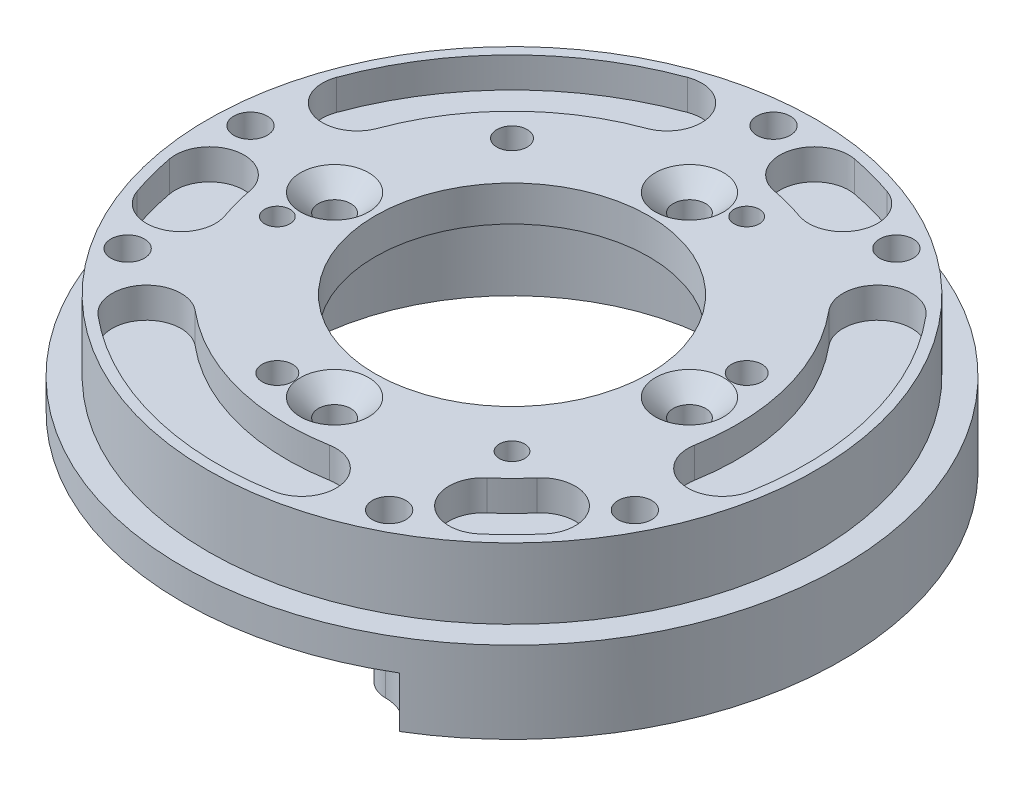
SolidWorks part; units mm, degrees
other "标注1"
sketch "草图29" plane through (-46.0426, 0, -48.8649) normal (-0.8494, -0.5243, -0.0612) x (-0.0248, 0.1556, -0.9875)
material "6060 合金"
ref_plane "前视基准面" through (0, 0, 0) normal (0, 0, 1) x (1, 0, 0)
ref_plane "上视基准面" through (0, 0, 0) normal (0, 1, 0) x (1, 0, 0)
ref_plane "右视基准面" through (0, 0, 0) normal (1, 0, 0) x (0, 0, -1)
other "Configuration Table"
sketch "草图28" plane through (0, 0, 0) normal (0, 1, 0) x (1, 0, 0)
  line L0 (-14.4782, -12.1487) -> (6.4642, -17.7602)
  line L1 (-27.2647, -3.5895) -> (21.8172, -16.7409)
  line L2 (-4.007, -14.9544) -> (-2.7238, -10.1652)
  line B0 (11.25, -19.4856) -> (13.9194, -24.1091)
  line B1 (-24.1091, -13.9194) -> (-20.8398, -12.0319)
  line B2 (-19.2037, -11.7247) -> (-18.8196, -12.0447)
  line B3 (-19.2037, -11.7247) -> (-18.2436, -10.5722)
  line B4 (-17.8595, -10.8923) -> (-18.2436, -10.5722)
  line B5 (-8.4473, -20.6856) -> (-18.8196, -12.0447)
  line B6 (-17.8595, -10.8923) -> (-17.2064, -11.4363)
  line B7 (-17.2064, -11.4363) -> (-16.5241, -10.6173)
  line B8 (-16.5241, -10.6173) -> (-16.7546, -10.4253)
  line B9 (-16.793, -10.0027) -> (-16.409, -9.5417)
  line B10 (-15.9865, -9.5033) -> (-15.756, -9.6953)
  line B11 (-6.6898, -17.2481) -> (-6.4593, -17.4401)
  line B12 (-6.4209, -17.8626) -> (-6.8049, -18.3236)
  line B13 (-7.2274, -18.3621) -> (-7.4579, -18.1701)
  line B14 (-7.4579, -18.1701) -> (-8.1402, -18.9891)
  line B15 (-8.1402, -18.9891) -> (-7.4872, -19.5332)
  line B16 (-7.103, -19.8532) -> (-8.0631, -21.0057)
  line B17 (-8.4473, -20.6856) -> (-8.0631, -21.0057)
  line B18 (-7.103, -19.8532) -> (-7.4872, -19.5332)
  line B19 (-12.8082, -19.6558) -> (-10.4573, -21.6142)
  line B20 (-12.8082, -19.6558) -> (-11.528, -18.1191)
  line B21 (-11.528, -18.1191) -> (-9.1772, -20.0776)
  line B22 (-9.1772, -20.0776) -> (-10.4573, -21.6142)
  line B23 (-15.7388, -14.6112) -> (-17.019, -16.1479)
  line B24 (-19.3698, -14.1894) -> (-17.019, -16.1479)
  line B25 (-17.019, -16.1479) -> (-15.7388, -14.6112)
  line B26 (-18.0897, -12.6528) -> (-15.7388, -14.6112)
  arc B27 (-28.8896, 2.5275) -> (-22.9125, 2.0046) centre (-25.9011, 2.266) ccw
  arc B28 (-20.8451, 9.7202) -> (-22.9125, 2.0046) centre (0, 0) ccw
  arc B29 (-20.8451, 9.7202) -> (-23.3025, 13.9767) centre (-23.564, 10.9881) ccw
  arc B30 (-23.3025, 13.9767) -> (-26.2829, 12.2559) centre (-23.564, 10.9881) ccw
  arc B31 (-26.2829, 12.2559) -> (-28.8896, 2.5275) centre (0, 0) ccw
  arc B32 (-18.6408, 22.2153) -> (-14.7841, 17.619) centre (-16.7125, 19.9172) ccw
  arc B33 (-7.8665, 21.6129) -> (-14.7841, 17.619) centre (0, 0) ccw
  arc B34 (-7.8665, 21.6129) -> (-8.6311, 27.4206) centre (-8.8925, 24.432) ccw
  arc B35 (-8.6311, 27.4206) -> (-9.9186, 27.2511) centre (-8.8925, 24.432) ccw
  arc B36 (-9.9186, 27.2511) -> (-18.6408, 22.2153) centre (0, 0) ccw
  arc B37 (2.5275, 28.8896) -> (2.0046, 22.9125) centre (2.266, 25.9011) ccw
  arc B38 (9.7202, 20.8451) -> (2.0046, 22.9125) centre (0, 0) ccw
  arc B39 (9.7202, 20.8451) -> (12.2559, 26.2829) centre (10.9881, 23.564) ccw
  arc B40 (12.2559, 26.2829) -> (2.5275, 28.8896) centre (0, 0) ccw
  arc B41 (-24.6935, -11.8811) -> (-24.1705, -5.9039) centre (-24.432, -8.8925) ccw
  arc B42 (20.1786, 19.7011) -> (17.619, 14.7841) centre (19.9172, 16.7125) ccw
  arc B43 (21.6129, 7.8665) -> (17.619, 14.7841) centre (0, 0) ccw
  arc B44 (21.6129, 7.8665) -> (27.2511, 9.9186) centre (24.432, 8.8925) ccw
  arc B45 (27.2511, 9.9186) -> (22.2153, 18.6408) centre (0, 0) ccw
  arc B46 (22.2153, 18.6408) -> (20.1786, 19.7011) centre (19.9172, 16.7125) ccw
  arc B47 (-24.1705, -5.9039) -> (-24.6935, -11.8811) centre (-24.432, -8.8925) ccw
  arc B48 (27.1209, 1.9457) -> (27.4085, 5.2332) centre (27.2647, 3.5895) ccw
  arc B49 (26.1625, 0.7225) -> (22.9125, -2.0046) centre (25.9011, -2.266) ccw
  arc B50 (20.8451, -9.7202) -> (22.9125, -2.0046) centre (0, 0) ccw
  arc B51 (20.8451, -9.7202) -> (26.2829, -12.2559) centre (23.564, -10.9881) ccw
  arc B52 (26.2829, -12.2559) -> (28.8896, -2.5275) centre (0, 0) ccw
  arc B53 (28.8896, -2.5275) -> (26.1625, 0.7225) centre (25.9011, -2.266) ccw
  arc B54 (27.4085, 5.2332) -> (27.1209, 1.9457) centre (27.2647, 3.5895) ccw
  arc B55 (16.5971, 20.1735) -> (16.8847, 23.4609) centre (16.7409, 21.8172) ccw
  arc B56 (16.8847, 23.4609) -> (16.5971, 20.1735) centre (16.7409, 21.8172) ccw
  arc B57 (-3.7333, 25.621) -> (-3.4457, 28.9085) centre (-3.5895, 27.2647) ccw
  arc B58 (-3.4457, 28.9085) -> (-3.7333, 25.621) centre (-3.5895, 27.2647) ccw
  arc B59 (-21.961, 15.0972) -> (-21.6734, 18.3847) centre (-21.8172, 16.7409) ccw
  arc B60 (-21.6734, 18.3847) -> (-21.961, 15.0972) centre (-21.8172, 16.7409) ccw
  arc B61 (-27.4085, -5.2332) -> (-27.1209, -1.9457) centre (-27.2647, -3.5895) ccw
  arc B62 (-27.1209, -1.9457) -> (-27.4085, -5.2332) centre (-27.2647, -3.5895) ccw
  arc B63 (21.6734, -18.3847) -> (21.961, -15.0972) centre (21.8172, -16.7409) ccw
  arc B64 (21.961, -15.0972) -> (21.6734, -18.3847) centre (21.8172, -16.7409) ccw
  arc B65 (16.451, -22.9057) -> (16.9739, -16.9286) centre (16.7125, -19.9172) ccw
  arc B66 (16.9739, -16.9286) -> (16.451, -22.9057) centre (16.7125, -19.9172) ccw
  arc B67 (-16.793, -10.0027) -> (-16.7546, -10.4253) centre (-16.5626, -10.1948) ccw
  arc B68 (-15.9865, -9.5033) -> (-16.409, -9.5417) centre (-16.1785, -9.7338) ccw
  arc B69 (-25.8706, -14.3099) -> (-24.1091, -13.9194) centre (-25.6091, -11.3213) ccw
  arc B70 (-27.1512, -13.8946) -> (-25.8706, -14.3099) centre (-25.6091, -11.3213) ccw
  arc B71 (16.5663, -25.6087) -> (-27.1512, -13.8946) centre (0, 0) ccw
  arc B72 (16.256, -25.5977) -> (16.5663, -25.6087) centre (16.5175, -22.6091) ccw
  arc B73 (13.9194, -24.1091) -> (16.256, -25.5977) centre (16.5175, -22.6091) ccw
  arc B74 (11.25, -19.4856) -> (-19.703, -10.8647) centre (0, 0) ccw
  arc B75 (-20.8398, -12.0319) -> (-19.703, -10.8647) centre (-22.3398, -9.4338) ccw
  arc B76 (-15.756, -9.6953) -> (-6.6898, -17.2481) centre (0, 0) ccw
  arc B77 (-6.4209, -17.8626) -> (-6.4593, -17.4401) centre (-6.6514, -17.6706) ccw
  arc B78 (-7.2274, -18.3621) -> (-6.8049, -18.3236) centre (-7.0354, -18.1316) ccw
sketch_block_instance "块1-1"
sketch_block "块1"
sketch "草图3" plane through (0, 0, 0) normal (0, 1, 0) x (1, 0, 0)
  line L1 (-50, -50) -> (50, -50)
  line L2 (-50, -50) -> (-50, 50)
  line L3 (-50, 50) -> (50, 50)
  line L4 (50, -50) -> (50, 50)
  line L5 (0, 50) -> (0, -50) construction
  line L6 (-50, 0) -> (50, 0) construction
  point P0 (0, 0)
  dimension "D1" = 100
sketch "草图1" plane through (0, 0, 0) normal (0, 1, 0) x (1, 0, 0)
  circle A0 centre (0, 0) radius 29.98
  circle A3 centre (0, 0) radius 21.1
  point P13 (0, 0)
  dimension "D1" = 59.96
  dimension "D3" = 42.2
extrude "凸台-拉伸1" add sketch "草图1" along normal blind 10.5
sketch "草图2" plane through (0, 10.5, 0) normal (0, 1, 0) x (1, 0, 0)
  circle A0 centre (0, 0) radius 29.98
  circle A2 centre (0, 0) radius 29.98 construction
extrude "切除-拉伸1" cut sketch "草图2" against normal blind 0.5
sketch "草图9" plane through (0, 10, 0) normal (0, 1, 0) x (1, 0, 0)
  circle A0 centre (0, 0) radius 13.5
  circle A2 centre (0, 0) radius 21.15
  dimension "D1" = 27
  dimension "D2" = 42.3
extrude "凸台-拉伸4" add sketch "草图9" against normal blind 3.5
sketch "草图6" plane through (0, 10, 0) normal (0, 1, 0) x (1, 0, 0)
  circle A0 centre (0, 0) radius 17.5 construction
  circle A1 centre (0, 17.5) radius 1.6
  circle A2 centre (17.5, 0) radius 1.6
  circle A3 centre (0, -17.5) radius 1.6
  circle A4 centre (-17.5, 0) radius 1.6
  point P14 (0, 0)
  dimension "D1" = 35
  dimension "D2" = 3.2
  dimension "D3" = 4
hole_wizard "M3 六角凹锥坑螺钉的锥形沉头孔3" positions "3D草图1" profile "草图14" countersink size "M3" standard "ISO"
sketch3d "3D草图1"
  point P0 (17.5, 10, 0)
  point P3 (0, 10, 17.5)
  point P6 (0, 10, -17.5)
  point P9 (-17.5, 10, 0)
sketch "草图14" plane through (17.5, 10, 0) normal (1, 0, 0) x (0, 0, 1)
  line L0 (0, 0) -> (0, 5)
  line L1 (0, 5) -> (1.6, 4.0386)
  line L2 (1.6, 4.0386) -> (1.6, 1.76)
  line L3 (1.6, 1.76) -> (3.36, 0)
  line L5 (3.36, 0) -> (0, 0)
  line L6 (-1.6, 1.76) -> (-3.36, 0) construction
  line L10 (0, 5) -> (-1.6, 4.0386) construction
  line L11 (0, -6.35) -> (0, 107.95) construction
  dimension "孔直径" = 3.2
  dimension "孔深度" = 5
  dimension "近端锥形沉头孔直径" = 6.72
  dimension "近端锥形沉头孔角度" = 90
  dimension "导头角度" = 118
sketch "草图7" plane through (0, 10, 0) normal (0, 1, 0) x (1, 0, 0)
  line L0 (0, 0) -> (-4.8917, -18.256) construction
  line L1 (0, 17.5) -> (0, 0) construction
  line L2 (0, 0) -> (17.5, 0) construction
  line L3 (17.5, 0) -> (-18.256, -4.8917) construction
  line L4 (-18.256, -4.8917) -> (0, 0) construction
  line L5 (-4.8917, -18.256) -> (0, 17.5) construction
  circle A0 centre (0, 0) radius 18.9 construction
  circle A1 centre (-4.8917, -18.256) radius 1.5
  circle A2 centre (-18.256, -4.8917) radius 1.5
  circle A3 centre (-13.3643, 13.3643) radius 1.5
  circle A4 centre (4.8917, 18.256) radius 1.5
  circle A5 centre (18.256, 4.8917) radius 1.5
  circle A6 centre (13.3643, -13.3643) radius 1.5
  point P7 (-18.256, -4.8917)
  point P11 (0, 0)
  point P16 (4.8917, 18.256)
  point P20 (13.3643, -13.3643)
  point P24 (-18.256, -4.8917)
  dimension "D1" = 37.8
  dimension "D2" = 3
  dimension "D3" = 6
hole_wizard "M3 螺纹孔1" positions "草图7" profile "草图22" tap size "M3" standard "ISO"
sketch "草图22" plane through (-18.256, 10, 4.8917) normal (1, 0, 0) x (0, 0, 1)
  line L0 (0, 0) -> (0, 7.5)
  line L1 (0, 7.5) -> (1.25, 6.7489)
  line L2 (1.25, 6.7489) -> (1.25, 0)
  line L5 (1.25, 0) -> (0, 0)
  line L10 (0, 7.5) -> (-1.25, 6.7489) construction
  line L11 (0, -6.35) -> (0, 107.95) construction
  dimension "螺纹孔钻头直径" = 2.5
  dimension "螺纹孔钻头深度" = 7.5
  dimension "导头角度" = 118
cosmetic thread "孔螺纹线1" parameters "D1"=6, "D2"=3
cosmetic thread "孔螺纹线2" parameters "D1"=6, "D2"=3
cosmetic thread "孔螺纹线3" parameters "D1"=6, "D2"=3
sketch "草图11" plane through (0, 0, 0) normal (0, -1, 0) x (1, 0, 0)
  circle A0 centre (0, 0) radius 32.5
  circle A2 centre (0, 0) radius 29.98 construction
  circle A3 centre (0, 0) radius 29.98
  dimension "D1" = 65
extrude "凸台-拉伸6" add sketch "草图11" against normal blind 3
sketch "草图12" plane through (0, 0, 0) normal (0, -1, 0) x (1, 0, 0)
  line L1 (-20.2826, 5.8159) -> (-28.0688, 8.0486)
  line L2 (8.5821, 19.2758) -> (11.8767, 26.6755)
  line L3 (0, 0) -> (-20.2826, 5.8159) construction
  line L4 (0, 0) -> (8.5821, 19.2758) construction
  line L5 (11.8767, 26.6755) -> (13.2189, 29.6902) construction
  line L6 (-8.9172, 19.1231) -> (0, 0) construction
  circle A0 centre (0, 0) radius 32.5 construction
  arc A1 (-28.0688, 8.0486) -> (11.8767, 26.6755) centre (0, 0) cw
  arc A2 (-20.2826, 5.8159) -> (8.5821, 19.2758) centre (0, 0) cw
  circle A3 centre (0, 0) radius 21.1 construction
  circle M1 centre (0, 0) radius 21.1
  dimension "D3" = 29.2
  dimension "D1" = 98
  dimension "D2" = 74
extrude "切除-拉伸4" cut sketch "草图12" against normal blind 4.5 contours A1 L1 L2 M1 region at (-9.4609, 0, 20.2889)
extrude "切除-拉伸7" cut sketch "草图7<2>" against normal through all contours A3 | A5 | A1 region at (-4.8917, 10, 18.256) region at (-13.3643, 10, -13.3643) region at (18.256, 10, -4.8917)
sketch "草图7<2>" plane through (0, 10, 0) normal (0, 1, 0) x (1, 0, 0) same geometry as "草图7"
sketch "草图23" plane through (0, 10, 0) normal (0, 1, 0) x (1, 0, 0)
  circle A0 centre (-13.3643, 13.3643) radius 3
  circle A1 centre (-4.8917, -18.256) radius 3
  circle A2 centre (18.256, 4.8917) radius 3
  dimension "D1" = 6
sketch "草图25" plane through (0, 6.5, 0) normal (0, -1, 0) x (1, 0, 0)
  circle A0 centre (18.256, -4.8917) radius 1.5 construction
  circle A1 centre (-13.3643, -13.3643) radius 1.5 construction
  circle A2 centre (-4.8917, 18.256) radius 1.5 construction
  circle A3 centre (18.256, -4.8917) radius 1.5
  circle A4 centre (-13.3643, -13.3643) radius 1.5
  circle A5 centre (-4.8917, 18.256) radius 1.5
extrude "凸台-拉伸7" add sketch "草图25" against normal blind 1
sketch "草图30" plane through (0, 0, 0) normal (0, -1, 0) x (1, 0, 0)
  line L0 (-20.2826, 5.8159) -> (-28.0688, 8.0486) construction
  line L1 (-20.2826, 5.8159) -> (-31.241, 8.9582)
  line L2 (8.5821, 19.2758) -> (11.8767, 26.6755) construction
  line L3 (8.5821, 19.2758) -> (13.2189, 29.6902)
  circle A0 centre (-27.2647, 3.5895) radius 2
  circle A1 centre (-21.8172, -16.7409) radius 2
  circle A2 centre (-3.5895, -27.2647) radius 2
  circle A3 centre (16.7409, -21.8172) radius 2
  circle A4 centre (27.2647, -3.5895) radius 2
  circle A5 centre (21.8172, 16.7409) radius 2
  circle A7 centre (0, 0) radius 32.5 construction
  arc A8 (-31.241, 8.9582) -> (13.2189, 29.6902) centre (0, 0) ccw
  arc A9 (-20.2826, 5.8159) -> (8.5821, 19.2758) centre (0, 0) ccw construction
  arc A10 (-20.2826, 5.8159) -> (8.5821, 19.2758) centre (0, 0) ccw
  dimension "D1" = 4
extrude "凸台-拉伸8" add sketch "草图30" along normal blind 5 contours A10 L3 A8 L1
sketch "草图33" plane through (0, -5, 0) normal (0, -1, 0) x (1, 0, 0)
  circle A0 centre (-27.2647, 3.5895) radius 2
  circle A1 centre (-21.8172, -16.7409) radius 2
  circle A2 centre (-3.5895, -27.2647) radius 2
  circle A3 centre (16.7409, -21.8172) radius 2
  circle A4 centre (27.2647, -3.5895) radius 2
  circle A5 centre (21.8172, 16.7409) radius 2
  dimension "D1" = 4
fillet "圆角1" radius 4 2 edges at (8.5821, -0.25, 19.2758) (-20.2826, -0.25, 5.8159)
fillet "圆角2" radius 3.5 2 edges at (11.8767, 2.25, 26.6755) (-28.0688, 2.25, 8.0486)
sketch "草图36" plane through (0, 0, 0) normal (0, -1, 0) x (1, 0, 0)
  line L0 (-31.241, 8.9582) -> (-31.2218, 8.9527)
  line L1 (13.2189, 29.6902) -> (13.2108, 29.672)
  arc A0 (13.2189, 29.6902) -> (-31.241, 8.9582) centre (0, 0) ccw construction
  arc A1 (13.2189, 29.6902) -> (-31.241, 8.9582) centre (0, 0) ccw
  arc A2 (13.2108, 29.672) -> (-31.2218, 8.9527) centre (0, 0) ccw
  dimension "D1" = 0.02
extrude "凸台-拉伸9" add sketch "草图36" along normal through all
sketch "草图43" plane through (0, -5, 0) normal (0, -1, 0) x (1, 0, 0)
  arc A3 (13.2108, 29.672) -> (-31.2218, 8.9527) centre (0, 0) ccw construction
  arc A4 (16.7579, 27.8231) -> (-32.0855, 5.0471) centre (0, 0) ccw
  circle A5 centre (-31.2218, 8.9527) radius 4
  circle A6 centre (13.2108, 29.672) radius 4
  line M4 (-23.8193, 6.8301) -> (-31.2218, 8.9527)
  line M6 (13.2108, 29.672) -> (10.0786, 22.6369)
  dimension "D1" = 8
extrude "切除-拉伸10" cut sketch "草图43" against normal up to surface (5 mm away) contours A4 A5 M4 | A6 A4 M6 region at (14.0216, -5, 27.405) region at (-30.0063, -5, 6.8744) up to face at (-9.7464, 0, 20.9013)
sketch "草图40" plane through (0, 10, 0) normal (0, 1, 0) x (1, 0, 0)
  line L0 (-4.8917, -18.256) -> (-13.3643, 13.3643) construction
  line L1 (0, 0) -> (-9.128, -2.4458) construction
  circle A0 centre (-13.3643, 13.3643) radius 13.8 construction
  circle A1 centre (18.256, 4.8917) radius 13.8 construction
  circle A2 centre (-4.8917, -18.256) radius 13.8 construction
  circle A3 centre (-27.3363, 1.546) radius 2
  circle A4 centre (-27.3363, 1.546) radius 3.9 construction
  circle A5 centre (-22.901, -15.007) radius 2
  circle A8 centre (0, 0) radius 29.98 construction
  circle A9 centre (15.007, 22.901) radius 2
  circle A10 centre (-1.546, 27.3363) radius 2
  circle A11 centre (12.3293, -24.4469) radius 2
  circle A12 centre (24.4469, -12.3293) radius 2
  point P29 (0, 0)
  dimension "D1" = 27.6
  dimension "D2" = 4
  dimension "D3" = 7.8
  dimension "D4" = 0.6
  dimension "D5" = 0.6
  dimension "D6" = 3
hole_wizard "M4 螺纹孔1" positions "3D草图2" profile "草图32" tap size "M4" standard "ISO"
sketch3d "3D草图2"
  point P9 (-27.2647, -5, 3.5895)
  point P12 (-21.8172, -5, -16.7409)
  point P15 (-3.5895, -5, -27.2647)
  point P18 (16.7409, -5, -21.8172)
  point P21 (27.2647, -5, -3.5895)
  point P24 (21.8172, -5, 16.7409)
  point P27 (-27.3363, 10, -1.546)
  point P30 (-22.901, 10, 15.007)
  point P33 (12.3293, 10, 24.4469)
  point P36 (24.4469, 10, 12.3293)
  point P39 (15.007, 10, -22.901)
  point P42 (-1.546, 10, -27.3363)
sketch "草图32" plane through (-27.2647, -5, 3.5895) normal (1, 0, 0) x (0, 0, -1)
  line L0 (0, 0) -> (0, 7.5)
  line L1 (0, 7.5) -> (1.65, 6.5086)
  line L2 (1.65, 6.5086) -> (1.65, 0)
  line L5 (1.65, 0) -> (0, 0)
  line L10 (0, 7.5) -> (-1.65, 6.5086) construction
  line L11 (0, -6.35) -> (0, 107.95) construction
  dimension "螺纹孔钻头直径" = 3.3
  dimension "螺纹孔钻头深度" = 7.5
  dimension "导头角度" = 118
cosmetic thread "孔螺纹线28" parameters "D1"=8, "D2"=4
cosmetic thread "孔螺纹线29" parameters "D1"=8, "D2"=4
cosmetic thread "孔螺纹线30" parameters "D1"=8, "D2"=4
cosmetic thread "孔螺纹线31" parameters "D1"=8, "D2"=4
cosmetic thread "孔螺纹线32" parameters "D1"=8, "D2"=4
cosmetic thread "孔螺纹线33" parameters "D1"=8, "D2"=4
cosmetic thread "孔螺纹线34" parameters "D1"=8, "D2"=4
cosmetic thread "孔螺纹线35" parameters "D1"=8, "D2"=4
cosmetic thread "孔螺纹线36" parameters "D1"=8, "D2"=4
cosmetic thread "孔螺纹线37" parameters "D1"=8, "D2"=4
cosmetic thread "孔螺纹线39" parameters "D1"=8, "D2"=4
cosmetic thread "孔螺纹线40" parameters "D1"=8, "D2"=4
sketch "草图37" plane through (0, -5, 0) normal (0, -1, 0) x (1, 0, 0)
  line L0 (-27.2647, 3.5895) -> (-21.8172, -16.7409) construction
  line L1 (-26.08, -6.9881) -> (-24.541, -6.5757) construction
  arc A0 (-26.6297, -4.4563) -> (-25.2901, -9.4556) centre (0, 0) ccw construction
  arc A1 (-31.5611, -5.2815) -> (-29.9735, -11.2066) centre (0, 0) ccw
  arc A2 (-21.6983, -3.631) -> (-20.6068, -7.7046) centre (0, 0) ccw
  arc A3 (-21.6983, -3.631) -> (-31.5611, -5.2815) centre (-26.6297, -4.4563) ccw
  arc A4 (-29.9735, -11.2066) -> (-20.6068, -7.7046) centre (-25.2901, -9.4556) ccw
  arc A21 (26.6297, 4.4563) -> (25.2901, 9.4556) centre (0, 0) ccw construction
  arc A22 (31.5611, 5.2815) -> (29.9735, 11.2066) centre (0, 0) ccw
  arc A23 (21.6983, 3.631) -> (20.6068, 7.7046) centre (0, 0) ccw
  arc A24 (21.6983, 3.631) -> (31.5611, 5.2815) centre (26.6297, 4.4563) ccw
  arc A25 (29.9735, 11.2066) -> (20.6068, 7.7046) centre (25.2901, 9.4556) ccw
  arc A26 (21.9811, -15.679) -> (24.569, -11.1967) centre (0, 0) ccw construction
  arc A27 (26.0517, -18.5825) -> (29.1188, -13.2702) centre (0, 0) ccw
  arc A28 (17.9105, -12.7755) -> (20.0191, -9.1233) centre (0, 0) ccw
  arc A29 (17.9105, -12.7755) -> (26.0517, -18.5825) centre (21.9811, -15.679) ccw
  arc A30 (29.1188, -13.2702) -> (20.0191, -9.1233) centre (24.569, -11.1967) ccw
  arc A31 (4.4563, -26.6297) -> (9.4556, -25.2901) centre (0, 0) ccw construction
  arc A32 (5.2815, -31.5611) -> (11.2066, -29.9735) centre (0, 0) ccw
  arc A33 (3.631, -21.6983) -> (7.7046, -20.6068) centre (0, 0) ccw
  arc A34 (3.631, -21.6983) -> (5.2815, -31.5611) centre (4.4563, -26.6297) ccw
  arc A35 (11.2066, -29.9735) -> (7.7046, -20.6068) centre (9.4556, -25.2901) ccw
  arc A36 (-15.679, -21.9811) -> (-11.1967, -24.569) centre (0, 0) ccw construction
  arc A37 (-18.5825, -26.0517) -> (-13.2702, -29.1188) centre (0, 0) ccw
  arc A38 (-12.7755, -17.9105) -> (-9.1233, -20.0191) centre (0, 0) ccw
  arc A39 (-12.7755, -17.9105) -> (-18.5825, -26.0517) centre (-15.679, -21.9811) ccw
  arc A40 (-13.2702, -29.1188) -> (-9.1233, -20.0191) centre (-11.1967, -24.569) ccw
  arc A1196 (-21.9811, 15.679) -> (-24.569, 11.1967) centre (0, 0) ccw construction
  arc A1197 (-26.0517, 18.5825) -> (-29.1188, 13.2702) centre (0, 0) ccw
  arc A1198 (-17.9105, 12.7755) -> (-20.0191, 9.1233) centre (0, 0) ccw
  arc A1199 (-17.9105, 12.7755) -> (-26.0517, 18.5825) centre (-21.9811, 15.679) ccw
  arc A1200 (-29.1188, 13.2702) -> (-20.0191, 9.1233) centre (-24.569, 11.1967) ccw
  arc A1201 (-4.4563, 26.6297) -> (-9.4556, 25.2901) centre (0, 0) ccw construction
  arc A1202 (-5.2815, 31.5611) -> (-11.2066, 29.9735) centre (0, 0) ccw
  arc A1203 (-3.631, 21.6983) -> (-7.7046, 20.6068) centre (0, 0) ccw
  arc A1204 (-3.631, 21.6983) -> (-5.2815, 31.5611) centre (-4.4563, 26.6297) ccw
  arc A1205 (-11.2066, 29.9735) -> (-7.7046, 20.6068) centre (-9.4556, 25.2901) ccw
  arc A1206 (15.679, 21.9811) -> (11.1967, 24.569) centre (0, 0) ccw construction
  arc A1207 (18.5825, 26.0517) -> (13.2702, 29.1188) centre (0, 0) ccw
  arc A1208 (12.7755, 17.9105) -> (9.1233, 20.0191) centre (0, 0) ccw
  arc A1209 (12.7755, 17.9105) -> (18.5825, 26.0517) centre (15.679, 21.9811) ccw
  arc A1210 (13.2702, 29.1188) -> (9.1233, 20.0191) centre (11.1967, 24.569) ccw
  point P3 (-26.08, -6.9881)
  point P21 (-24.2737, 8.7422)
  point P28 (-10.9825, 23.3458)
  point P35 (8.7422, 24.2737)
  point P42 (26.08, 6.9881)
  point P49 (23.3827, -13.5)
  point P56 (6.9881, -26.08)
  point P63 (-13.5, -23.3827)
  point P68 (0, 0)
  point P72 (-24.2737, 8.7422)
  point P80 (-10.9825, 23.3458)
  point P88 (8.7422, 24.2737)
  point P96 (-24.2737, 8.7422)
  point P104 (-10.9825, 23.3458)
  point P112 (8.7422, 24.2737)
  point P120 (-24.2737, 8.7422)
  point P128 (-10.9825, 23.3458)
  point P136 (8.7422, 24.2737)
  point P144 (-24.2737, 8.7422)
  point P152 (-10.9825, 23.3458)
  point P160 (8.7422, 24.2737)
  point P168 (-24.2737, 8.7422)
  point P176 (-10.9825, 23.3458)
  point P184 (8.7422, 24.2737)
  point P192 (-24.2752, 8.7381)
  point P200 (-10.9864, 23.3439)
  point P208 (8.7381, 24.2752)
  point P217 (-24.2752, 8.7381)
  point P225 (-10.9864, 23.3439)
  point P233 (8.7381, 24.2752)
  point P241 (-24.2752, 8.7381)
  point P249 (-10.9864, 23.3439)
  point P257 (8.7381, 24.2752)
  point P265 (-24.2752, 8.7381)
  point P273 (-10.9864, 23.3439)
  point P281 (8.7381, 24.2752)
  point P289 (-24.2752, 8.7381)
  point P297 (-10.9864, 23.3439)
  point P305 (8.7381, 24.2752)
  point P313 (-24.2752, 8.7381)
  point P321 (-10.9864, 23.3439)
  point P329 (8.7381, 24.2752)
  point P337 (-24.2752, 8.7381)
  point P345 (-10.9864, 23.3439)
  point P353 (8.7381, 24.2752)
  point P361 (-24.2752, 8.7381)
  point P369 (-10.9864, 23.3439)
  point P377 (8.7381, 24.2752)
  point P385 (-24.2752, 8.7381)
  point P393 (-10.9864, 23.3439)
  point P401 (8.7381, 24.2752)
  point P409 (-25.4043, 9.1445)
  point P417 (-11.4974, 24.4297)
  point P425 (9.1445, 25.4043)
  point P433 (-25.4043, 9.1445)
  point P441 (-11.4974, 24.4297)
  point P449 (9.1445, 25.4043)
  point P457 (-25.4043, 9.1445)
  point P465 (-11.4974, 24.4297)
  point P473 (9.1445, 25.4043)
  point P481 (-25.4043, 9.1445)
  point P489 (-11.4974, 24.4297)
  point P497 (9.1445, 25.4043)
  point P505 (-25.4043, 9.1445)
  point P513 (-11.4974, 24.4297)
  point P521 (9.1445, 25.4043)
  point P529 (-25.4043, 9.1445)
  point P537 (-11.4974, 24.4297)
  point P545 (9.1445, 25.4043)
  point P553 (-25.4043, 9.1445)
  point P561 (-11.4974, 24.4297)
  point P569 (9.1445, 25.4043)
  point P577 (-25.4043, 9.1445)
  point P585 (-11.4974, 24.4297)
  point P593 (9.1445, 25.4043)
  point P601 (-25.4043, 9.1445)
  point P609 (-11.4974, 24.4297)
  point P617 (9.1445, 25.4043)
  point P625 (-25.4043, 9.1445)
  point P633 (-11.4974, 24.4297)
  point P641 (9.1445, 25.4043)
  point P649 (-25.4043, 9.1445)
  point P657 (-11.4974, 24.4297)
  point P665 (9.1445, 25.4043)
  point P673 (-25.4043, 9.1445)
  point P681 (-11.4974, 24.4297)
  point P689 (9.1445, 25.4043)
  point P697 (-25.4043, 9.1445)
  point P705 (-11.4974, 24.4297)
  point P713 (9.1445, 25.4043)
  point P721 (-25.4043, 9.1445)
  point P729 (-11.4974, 24.4297)
  point P737 (9.1445, 25.4043)
  point P745 (-25.4043, 9.1445)
  point P753 (-11.4974, 24.4297)
  point P761 (9.1445, 25.4043)
  point P769 (-25.4043, 9.1445)
  point P777 (-11.4974, 24.4297)
  point P785 (9.1445, 25.4043)
  point P793 (-25.4043, 9.1445)
  point P801 (-11.4974, 24.4297)
  point P809 (9.1445, 25.4043)
  point P817 (-25.4043, 9.1445)
  point P825 (-11.4974, 24.4297)
  point P833 (9.1445, 25.4043)
  point P841 (-25.4043, 9.1445)
  point P849 (-11.4974, 24.4297)
  point P857 (9.1445, 25.4043)
  point P865 (-25.4043, 9.1445)
  point P873 (-11.4974, 24.4297)
  point P881 (9.1445, 25.4043)
  point P889 (-25.4043, 9.1445)
  point P897 (-11.4974, 24.4297)
  point P905 (9.1445, 25.4043)
  point P913 (-25.4043, 9.1445)
  point P921 (-11.4974, 24.4297)
  point P929 (9.1445, 25.4043)
  point P937 (-25.4043, 9.1445)
  point P945 (-11.4974, 24.4297)
  point P953 (9.1445, 25.4043)
  point P961 (-25.4043, 9.1445)
  point P969 (-11.4974, 24.4297)
  point P977 (9.1445, 25.4043)
  point P985 (-25.4043, 9.1445)
  point P993 (-11.4974, 24.4297)
  point P1001 (9.1445, 25.4043)
  point P1009 (-25.4043, 9.1445)
  point P1017 (-11.4974, 24.4297)
  point P1025 (9.1445, 25.4043)
  point P1033 (-25.4043, 9.1445)
  point P1041 (-11.4974, 24.4297)
  point P1049 (9.1445, 25.4043)
  point P1057 (-25.4043, 9.1445)
  point P1065 (-11.4974, 24.4297)
  point P1073 (9.1445, 25.4043)
  point P1081 (-25.4043, 9.1445)
  point P1089 (-11.4974, 24.4297)
  point P1097 (9.1445, 25.4043)
  point P1105 (-25.4043, 9.1445)
  point P1113 (-11.4974, 24.4297)
  point P1121 (9.1445, 25.4043)
  point P1129 (-25.4043, 9.1445)
  point P1137 (-11.4974, 24.4297)
  point P1145 (9.1445, 25.4043)
  point P1153 (-25.4043, 9.1445)
  point P1161 (-11.4974, 24.4297)
  point P1169 (9.1445, 25.4043)
  point P1177 (-25.4043, 9.1445)
  point P1185 (-11.4974, 24.4297)
  point P1193 (9.1445, 25.4043)
  point P1201 (-25.4043, 9.1445)
  point P1209 (-11.4974, 24.4297)
  point P1217 (9.1445, 25.4043)
  point P1225 (-25.4043, 9.1445)
  point P1233 (-11.4974, 24.4297)
  point P1241 (9.1445, 25.4043)
  point P1249 (-25.4043, 9.1445)
  point P1257 (-11.4974, 24.4297)
  point P1265 (9.1445, 25.4043)
  point P1273 (-25.4043, 9.1445)
  point P1281 (-11.4974, 24.4297)
  point P1289 (9.1445, 25.4043)
  point P1297 (-23.3827, 13.5)
  point P1305 (-6.9881, 26.08)
  point P1313 (13.5, 23.3827)
  point P1321 (-23.3827, 13.5)
  point P1329 (-6.9881, 26.08)
  point P1337 (13.5, 23.3827)
  point P1345 (-23.3827, 13.5)
  point P1353 (-6.9881, 26.08)
  point P1361 (13.5, 23.3827)
  point P1369 (-23.3827, 13.5)
  point P1377 (-6.9881, 26.08)
  point P1385 (13.5, 23.3827)
  point P1393 (-23.3827, 13.5)
  point P1401 (-6.9881, 26.08)
  point P1409 (13.5, 23.3827)
  point P1417 (-23.3827, 13.5)
  point P1425 (-6.9881, 26.08)
  point P1433 (13.5, 23.3827)
  point P1441 (-23.3827, 13.5)
  point P1449 (-6.9881, 26.08)
  point P1457 (13.5, 23.3827)
  point P1465 (-23.3827, 13.5)
  point P1473 (-6.9881, 26.08)
  point P1481 (13.5, 23.3827)
  point P1489 (-23.3827, 13.5)
  point P1497 (-6.9881, 26.08)
  point P1505 (13.5, 23.3827)
  point P1513 (-23.3827, 13.5)
  point P1521 (-6.9881, 26.08)
  point P1529 (13.5, 23.3827)
  point P1537 (-23.3827, 13.5)
  point P1545 (-6.9881, 26.08)
  point P1553 (13.5, 23.3827)
  point P1561 (-23.3827, 13.5)
  point P1569 (-6.9881, 26.08)
  point P1577 (13.5, 23.3827)
  point P1585 (-23.3827, 13.5)
  point P1593 (-6.9881, 26.08)
  point P1601 (13.5, 23.3827)
  point P1609 (-23.3827, 13.5)
  point P1617 (-6.9881, 26.08)
  point P1625 (13.5, 23.3827)
  point P1633 (-23.3827, 13.5)
  point P1641 (-6.9881, 26.08)
  point P1649 (13.5, 23.3827)
  point P1657 (-23.3827, 13.5)
  point P1665 (-6.9881, 26.08)
  point P1673 (13.5, 23.3827)
  point P1681 (-23.3827, 13.5)
  point P1689 (-6.9881, 26.08)
  point P1697 (13.5, 23.3827)
  point P1705 (-23.3827, 13.5)
  point P1713 (-6.9881, 26.08)
  point P1721 (13.5, 23.3827)
  point P1729 (-23.3827, 13.5)
  point P1737 (-6.9881, 26.08)
  point P1745 (13.5, 23.3827)
  point P1753 (-23.3827, 13.5)
  point P1761 (-6.9881, 26.08)
  point P1769 (13.5, 23.3827)
  point P1777 (-23.3827, 13.5)
  point P1785 (-6.9881, 26.08)
  point P1793 (13.5, 23.3827)
  point P1801 (-23.3827, 13.5)
  point P1809 (-6.9881, 26.08)
  point P1817 (13.5, 23.3827)
  point P1825 (-23.3827, 13.5)
  point P1833 (-6.9881, 26.08)
  point P1841 (13.5, 23.3827)
  point P1849 (-23.3827, 13.5)
  point P1857 (-6.9881, 26.08)
  point P1865 (13.5, 23.3827)
  point P1873 (-23.3827, 13.5)
  point P1881 (-6.9881, 26.08)
  point P1889 (13.5, 23.3827)
  point P1897 (-23.3827, 13.5)
  point P1905 (-6.9881, 26.08)
  point P1913 (13.5, 23.3827)
  point P1921 (-23.3827, 13.5)
  point P1929 (-6.9881, 26.08)
  point P1937 (13.5, 23.3827)
  dimension "D1" = 27
  dimension "D2" = 5
  dimension "D3" = 11
  dimension "D4" = 8
chamfer "倒角2" [suppressed] distance 4 angle 45
sketch "草图39" plane through (0, -5, 0) normal (0, -1, 0) x (1, 0, 0)
  line L0 (-21.0644, 1.2254) -> (-32.4451, 1.8875) construction
  line L1 (-17.6296, -11.5934) -> (-27.1546, -17.8572) construction
  line L2 (0, 0) -> (-21.0644, 1.2254) construction
  line L3 (0, 0) -> (-17.6296, -11.5934) construction
  line L4 (-22.6982, -0.2823) -> (-30.8994, 0.1948)
  line L5 (-19.7984, -11.1047) -> (-26.6622, -15.6184)
  line L6 (-16.2497, 15.8505) -> (-21.7114, 21.9869) [skipped]
  line L7 (-21.8518, 6.1474) -> (-29.8969, 7.8092) [skipped]
  line L8 (-0.2823, 22.6982) -> (0.1948, 30.8994) [skipped]
  line L9 (-11.1047, 19.7984) -> (-15.6184, 26.6622) [skipped]
  line L10 (15.8505, 16.2497) -> (21.9869, 21.7114) [skipped]
  line L11 (6.1474, 21.8518) -> (7.8092, 29.8969) [skipped]
  line L12 (22.6982, 0.2823) -> (30.8994, -0.1948)
  line L13 (19.7984, 11.1047) -> (26.6622, 15.6184)
  line L14 (16.2497, -15.8505) -> (21.7114, -21.9869)
  line L15 (21.8518, -6.1474) -> (29.8969, -7.8092)
  line L16 (0.2823, -22.6982) -> (-0.1948, -30.8994)
  line L17 (11.1047, -19.7984) -> (15.6184, -26.6622)
  line L18 (-15.8505, -16.2497) -> (-21.9869, -21.7114)
  line L19 (-6.1474, -21.8518) -> (-7.8092, -29.8969)
  line L20 (0, 0) -> (27.1546, 17.8572) construction
  line L23 (15.3033, 16.766) -> (22.3133, 21.3758)
  line L24 (11.9057, 21.8235) -> (12.737, 23.6907)
  line L25 (11.0241, 19.8434) -> (12.737, 23.6907)
  circle A0 centre (0, 0) radius 32.5 construction
  circle A2 centre (-27.2647, 3.5895) radius 2 construction
  arc A3 (-20.9503, 2.5093) -> (11.5443, 17.6618) centre (0, 0) ccw construction
  arc A4 (-21.0644, 1.2254) -> (-17.6296, -11.5934) centre (0, 0) ccw construction
  arc A5 (-32.4451, 1.8875) -> (-27.1546, -17.8572) centre (0, 0) ccw construction
  arc A6 (-30.8994, 0.1948) -> (-26.6622, -15.6184) centre (0, 0) ccw
  arc A7 (-22.6982, -0.2823) -> (-19.7984, -11.1047) centre (0, 0) ccw
  arc A8 (-21.7114, 21.9869) -> (-29.8969, 7.8092) centre (0, 0) ccw [skipped]
  arc A9 (-16.2497, 15.8505) -> (-21.8518, 6.1474) centre (0, 0) ccw [skipped]
  arc A10 (0.1948, 30.8994) -> (-15.6184, 26.6622) centre (0, 0) ccw [skipped]
  arc A11 (-0.2823, 22.6982) -> (-11.1047, 19.7984) centre (0, 0) ccw [skipped]
  arc A12 (21.9869, 21.7114) -> (7.8092, 29.8969) centre (0, 0) ccw [skipped]
  arc A13 (15.8505, 16.2497) -> (6.1474, 21.8518) centre (0, 0) ccw [skipped]
  arc A14 (30.8994, -0.1948) -> (26.6622, 15.6184) centre (0, 0) ccw
  arc A15 (22.6982, 0.2823) -> (19.7984, 11.1047) centre (0, 0) ccw
  arc A16 (21.7114, -21.9869) -> (29.8969, -7.8092) centre (0, 0) ccw
  arc A17 (16.2497, -15.8505) -> (21.8518, -6.1474) centre (0, 0) ccw
  arc A18 (-0.1948, -30.8994) -> (15.6184, -26.6622) centre (0, 0) ccw
  arc A19 (0.2823, -22.6982) -> (11.1047, -19.7984) centre (0, 0) ccw
  arc A20 (-21.9869, -21.7114) -> (-7.8092, -29.8969) centre (0, 0) ccw
  arc A21 (-15.8505, -16.2497) -> (-6.1474, -21.8518) centre (0, 0) ccw
  arc A22 (11.0241, 19.8434) -> (15.3033, 16.766) centre (0, 0) cw
  arc A23 (12.737, 23.6907) -> (18.5314, 26.8987) centre (13.2108, 29.672) ccw
  arc A24 (12.737, 23.6907) -> (17.4944, 25.4707) centre (13.2108, 29.672) ccw
  circle A25 centre (-21.8172, -16.7409) radius 2 construction
  arc A26 (17.4944, 25.4707) -> (22.3133, 21.3758) centre (0, 0) cw
  point P50 (0, 0)
  dimension "D3" = 4
  dimension "D5" = 5.6
  dimension "D1" = 1.6
  dimension "D4" = 2
  dimension "D2" = 8
extrude "切除-拉伸8" cut sketch "草图39" against normal blind 4.5
fillet "圆角3" radius 3.8 20 edges at (-22.6982, -2.75, -0.2823) (-26.6622, -2.75, -15.6184) (-19.7984, -2.75, -11.1047) (-15.8505, -2.75, -16.2497) (-21.9869, -2.75, -21.7114) (-7.8092, -2.75, -29.8969) (-6.1474, -2.75, -21.8518) (0.2823, -2.75, -22.6982) (-0.1948, -2.75, -30.8994) (15.6184, -2.75, -26.6622) (11.1047, -2.75, -19.7984) (16.2497, -2.75, -15.8505) (21.7114, -2.75, -21.9869) (29.8969, -2.75, -7.8092) (21.8518, -2.75, -6.1474) (22.6982, -2.75, 0.2823) (30.8994, -2.75, -0.1948) (26.6622, -2.75, 15.6184) (19.7984, -2.75, 11.1047) (-30.8994, -2.75, 0.1948)
fillet "圆角6" radius 2.7 7 edges at (15.3033, -2.75, 16.766) (22.3133, -2.75, 21.3758) (12.737, -2.75, 23.6907) (11.0241, -2.75, 19.8434) (17.4944, -2.75, 25.4707) (-27.3767, -2.5, 7.8502) (11.5839, -2.5, 26.0178)
sketch "草图41" plane through (0, 10, 0) normal (0, 1, 0) x (1, 0, 0)
  line L0 (-27.3363, 1.546) -> (-1.546, 27.3363) construction
  line L1 (-14.4411, 14.4411) -> (-18.0878, 18.0878) construction
  line L2 (-22.901, -15.007) -> (-27.3363, 1.546) construction
  line L3 (-24.7084, -6.6206) -> (-25.1186, -6.7305) construction
  arc A0 (-24.0373, 8.7489) -> (-8.7489, 24.0373) centre (0, 0) cw construction
  arc A1 (-9.9117, 27.2323) -> (-27.2323, 9.9117) centre (0, 0) ccw
  arc A2 (-7.586, 20.8424) -> (-20.8424, 7.586) centre (0, 0) ccw
  arc A3 (-7.586, 20.8424) -> (-9.9117, 27.2323) centre (-8.7489, 24.0373) ccw
  arc A4 (-27.2323, 9.9117) -> (-20.8424, 7.586) centre (-24.0373, 8.7489) ccw
  arc A5 (-25.15, -4.6705) -> (-24.1158, -8.5302) centre (0, 0) ccw construction
  arc A6 (-28.4929, -5.2913) -> (-27.3212, -9.6641) centre (0, 0) ccw
  arc A7 (-21.8072, -4.0497) -> (-20.9104, -7.3964) centre (0, 0) ccw
  arc A8 (-21.8072, -4.0497) -> (-28.4929, -5.2913) centre (-25.15, -4.6705) ccw
  circle A9 centre (0, 0) radius 29.98 construction
  arc A10 (19.5954, 16.4425) -> (25.1914, -4.4419) centre (0, 0) cw construction
  arc A11 (28.5397, -5.0323) -> (22.2, 18.628) centre (0, 0) ccw
  arc A12 (21.843, -3.8515) -> (16.9909, 14.257) centre (0, 0) ccw
  arc A13 (21.843, -3.8515) -> (28.5397, -5.0323) centre (25.1914, -4.4419) ccw
  arc A14 (22.2, 18.628) -> (16.9909, 14.257) centre (19.5954, 16.4425) ccw
  arc A15 (4.4419, -25.1914) -> (-16.4425, -19.5954) centre (0, 0) cw construction
  arc A16 (-18.628, -22.2) -> (5.0323, -28.5397) centre (0, 0) ccw
  arc A17 (-14.257, -16.9909) -> (3.8515, -21.843) centre (0, 0) ccw
  arc A18 (-14.257, -16.9909) -> (-18.628, -22.2) centre (-16.4425, -19.5954) ccw
  arc A19 (5.0323, -28.5397) -> (3.8515, -21.843) centre (4.4419, -25.1914) ccw
  arc A20 (-27.3212, -9.6641) -> (-20.9104, -7.3964) centre (-24.1158, -8.5302) ccw
  circle A21 centre (0, 0) radius 25.58 construction
  arc A22 (7.3964, 20.9104) -> (4.0497, 21.8072) centre (0, 0) ccw
  arc A23 (7.3964, 20.9104) -> (9.6641, 27.3212) centre (8.5302, 24.1158) ccw
  arc A24 (5.2913, 28.4929) -> (4.0497, 21.8072) centre (4.6705, 25.15) ccw
  arc A25 (9.6641, 27.3212) -> (5.2913, 28.4929) centre (0, 0) ccw
  arc A26 (8.5302, 24.1158) -> (4.6705, 25.15) centre (0, 0) ccw construction
  arc A27 (14.4107, -16.8607) -> (16.8607, -14.4107) centre (0, 0) ccw
  arc A28 (14.4107, -16.8607) -> (18.8288, -22.0299) centre (16.6198, -19.4453) ccw
  arc A29 (22.0299, -18.8288) -> (16.8607, -14.4107) centre (19.4453, -16.6198) ccw
  arc A30 (18.8288, -22.0299) -> (22.0299, -18.8288) centre (0, 0) ccw
  arc A31 (16.6198, -19.4453) -> (19.4453, -16.6198) centre (0, 0) ccw construction
  point P4 (-18.0878, 18.0878)
  point P21 (24.7084, 6.6206)
  point P28 (-6.6206, -24.7084)
  point P33 (0, 0)
  point P36 (-24.7084, -6.6206)
  point P50 (6.6206, 24.7084)
  point P58 (18.0878, -18.0878)
  dimension "D1" = 3.4
  dimension "D3" = 1
  dimension "D5" = 3.4
  dimension "D2" = 50
  dimension "D6" = 4
  dimension "D4" = 3
extrude "切除-拉伸9" cut sketch "草图41" against normal blind 3 contours A1 A4 A2 A3 | A16 A19 A17 A18 | A11 A14 A12 A13 | A28 A30 A29 A27 | A23 A25 A24 A22 | A6 A20 A7 A8 region at (-17.3019, 10, -17.3019) region at (-24.6544, 10, 6.6061) region at (23.6348, 10, -6.3329) region at (-6.3329, 10, 23.6348) region at (6.6061, 10, -24.6544) region at (18.0483, 10, 18.0483)
other "移动面1" [suppressed] offset 1 parameters "D1"=1
chamfer "倒角3" distance 3 angle 45 3 edges at (-26.6794, 0, 8.8984) (10.3326, 0, 26.1573) (-12.3405, 0, 26.4642)
sketch "草图44" plane through (0, -5, 0) normal (0, -1, 0) x (1, 0, 0)
  arc A0 (13.1944, 25.672) -> (16.7579, 27.8231) centre (13.2108, 29.672) ccw construction
  arc A1 (-32.0855, 5.0471) -> (-28.1471, 6.3941) centre (-31.2218, 8.9527) ccw construction
  arc A2 (13.58, 25.689) -> (15.1994, 33.1426) centre (13.2108, 29.672) ccw
  arc A3 (-35.1587, 9.6602) -> (-28.1471, 6.3941) centre (-31.2218, 8.9527) ccw
  arc A4 (13.58, 25.689) -> (8.9688, 30.9257) centre (7.1583, 24.683) ccw construction
  arc A5 (8.9688, 30.9257) -> (-29.4555, 13.0082) centre (0, 0) ccw construction
  arc A6 (-29.4555, 13.0082) -> (-28.408, 6.1097) centre (-23.5095, 10.3823) ccw construction
  arc A7 (13.58, 25.689) -> (8.9688, 30.9257) centre (7.1583, 24.683) ccw
  arc A8 (8.9688, 30.9257) -> (-29.4555, 13.0082) centre (0, 0) ccw
  arc A9 (-29.4555, 13.0082) -> (-28.408, 6.1097) centre (-23.5095, 10.3823) ccw
  arc A10 (15.1994, 33.1426) -> (-35.1587, 9.6602) centre (0, 0) ccw
extrude "切除-拉伸11" cut sketch "草图44" against normal up to surface (5 mm away) and the other way through all contours A2 A10 A3 A9 A8 A7 region at (12.4957, -5, 29.3828) up to face at (-9.9841, 0, 21.411)
other "移动面2" face at (0, 3, -29.98) offset 0.05 parameters "D1"=0.05
sketch "草图45" plane through (0, -5, 0) normal (0, -1, 0) x (1, 0, 0)
  circle A0 centre (-27.2647, 3.5895) radius 2.435
  circle A1 centre (-16.7409, 21.8172) radius 2.435
  circle A2 centre (3.5895, 27.2647) radius 2.435
  circle A3 centre (21.8172, 16.7409) radius 2.435
  circle A4 centre (27.2647, -3.5895) radius 2.435
  circle A5 centre (16.7409, -21.8172) radius 2.435
  circle A6 centre (-3.5895, -27.2647) radius 2.435
  circle A7 centre (-21.8172, -16.7409) radius 2.435
  point P19 (0, 0)
  dimension "D1" = 4.87
  dimension "D2" = 8
extrude "切除-拉伸12" [suppressed] cut sketch "草图45" against normal up to surface (5 mm away) up to face at (-9.9858, 0, 21.4145)
